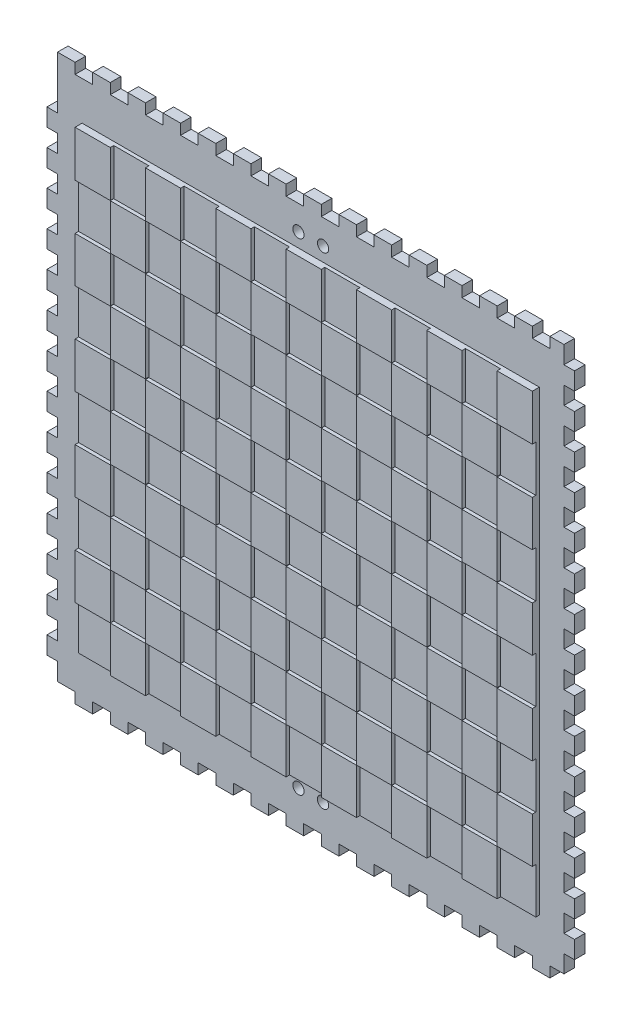
SolidWorks part; units mm, degrees
ref_plane "Front Plane" through (0, 0, 0) normal (0, 0, 1) x (1, 0, 0)
ref_plane "Top Plane" through (0, 0, 0) normal (0, 1, 0) x (1, 0, 0)
ref_plane "Right Plane" through (0, 0, 0) normal (1, 0, 0) x (0, 0, -1)
sketch "Sketch1" plane through (0, 0, 0) normal (0, 0, 1) x (1, 0, 0)
  line L1 (-75, 79) -> (75, 79)
  line L2 (-75, 79) -> (-75, -79)
  line L3 (-75, -79) -> (75, -79)
  line L4 (75, 79) -> (75, -79)
  line L5 (-75, 79) -> (75, -79) construction
  line L6 (-75, -79) -> (75, 79) construction
  point P0 (0, 0)
  dimension "D1" = 158
  dimension "D2" = 150
extrude "Boss-Extrude1" add sketch "Sketch1" along normal blind 5
sketch "Sketch2" plane through (0, 0, 5) normal (0, 0, 1) x (1, 0, 0)
  line L1 (-65, 65) -> (65, 65)
  line L2 (-65, 65) -> (-65, -65)
  line L3 (-65, -65) -> (65, -65)
  line L4 (65, 65) -> (65, -65)
  line L5 (-65, 65) -> (65, -65) construction
  line L6 (-65, -65) -> (65, 65) construction
  line L7 (-75, 79) -> (75, 79)
  line L8 (-75, 79) -> (-75, -79)
  line L9 (-75, -79) -> (75, -79)
  line L10 (75, 79) -> (75, -79)
  line L11 (-75, 79) -> (75, -79) construction
  line L12 (-75, -79) -> (75, 79) construction
  point P0 (0, 0)
  point P6 (0, 0)
  dimension "D1" = 130
  dimension "D2" = 130
extrude "Cut-Extrude1" cut sketch "Sketch2" against normal blind 2
sketch "Sketch3" plane through (0, 0, 5) normal (0, 0, 1) x (1, 0, 0)
  line L0 (-65, 65) -> (-65, -65) construction
  line L1 (-65, 51.95) -> (-55, 51.95)
  line L2 (-65, 51.95) -> (-65, 38.85)
  line L3 (-65, 38.85) -> (-55, 38.85)
  line L4 (-55, 51.95) -> (-55, 38.85)
  line L5 (65, 65) -> (-65, 65) construction
  dimension "D1" = 13.1
  dimension "D2" = 10
  dimension "D3" = 13.05
extrude "Cut-Extrude2" cut sketch "Sketch3" against normal blind 1
pattern_linear "LPattern1" count 7 spacing 20 along (1, 0, 0) count 5 spacing 26 along (0, -1, 0) of "Cut-Extrude2"
sketch "Sketch4" plane through (0, 0, 5) normal (0, 0, 1) x (1, 0, 0)
  line L0 (65, 65) -> (-65, 65) construction
  line L1 (-55, 65) -> (-45, 65)
  line L2 (-55, 65) -> (-55, 51.9)
  line L3 (-55, 51.9) -> (-45, 51.9)
  line L4 (-45, 65) -> (-45, 51.9)
  line L6 (-65, 65) -> (-65, -65) construction
  dimension "D1" = 10
  dimension "D2" = 10
  dimension "D3" = 13.1
extrude "Cut-Extrude3" cut sketch "Sketch4" against normal blind 1
pattern_linear "LPattern2" count 6 spacing 20 along (1, 0, 0) count 5 spacing 26 along (0, -1, 0) of "Cut-Extrude3"
sketch "Sketch5" plane through (0, 0, 3) normal (0, 0, 1) x (1, 0, 0)
  line L0 (-75, 79) -> (-75, -79) construction
  line L1 (-75, 64) -> (-72, 64)
  line L2 (-75, 64) -> (-75, 79)
  line L3 (-75, 79) -> (-72, 79)
  line L4 (-72, 64) -> (-72, 79)
  line L5 (75, 79) -> (-75, 79) construction
  dimension "D1" = 15
  dimension "D2" = 3
extrude "Cut-Extrude4" cut sketch "Sketch5" against normal blind 10
sketch "Sketch6" plane through (0, 0, 3) normal (0, 0, 1) x (1, 0, 0)
  line L0 (-75, 64) -> (-75, -79) construction
  line L1 (-75, 59) -> (-72, 59)
  line L2 (-75, 59) -> (-75, 54)
  line L3 (-75, 54) -> (-72, 54)
  line L4 (-72, 59) -> (-72, 54)
  line L5 (-75, 64) -> (-72, 64) construction
  dimension "D1" = 5
  dimension "D2" = 5
  dimension "D3" = 3
extrude "Cut-Extrude5" cut sketch "Sketch6" against normal blind 10
pattern_linear "LPattern3" count 14 spacing 10 along (0, -1, 0) of "Cut-Extrude5"
sketch "Sketch7" plane through (0, 0, 3) normal (0, 0, 1) x (1, 0, 0)
  line L1 (-72, -76) -> (-75, -76)
  line L2 (-72, -76) -> (-72, -79)
  line L3 (-72, -79) -> (-75, -79)
  line L4 (-75, -76) -> (-75, -79)
extrude "Cut-Extrude6" cut sketch "Sketch7" against normal blind 10
sketch "Sketch8" plane through (0, 0, 3) normal (0, 0, 1) x (1, 0, 0)
  line L1 (75, -79) -> (72, -79)
  line L2 (75, -79) -> (75, -71)
  line L3 (75, -71) -> (72, -71)
  line L4 (72, -79) -> (72, -71)
  dimension "D1" = 3
  dimension "D2" = 8
extrude "Cut-Extrude7" cut sketch "Sketch8" against normal blind 10
sketch "Sketch9" plane through (0, 0, 3) normal (0, 0, 1) x (1, 0, 0)
  line L0 (75, -71) -> (75, 79) construction
  line L1 (75, -66) -> (72, -66)
  line L2 (75, -66) -> (75, -61)
  line L3 (75, -61) -> (72, -61)
  line L4 (72, -66) -> (72, -61)
  line L5 (75, -71) -> (72, -71) construction
  dimension "D1" = 5
  dimension "D2" = 5
  dimension "D3" = 3
extrude "Cut-Extrude8" cut sketch "Sketch9" against normal blind 10
pattern_linear "LPattern4" count 15 spacing 10 along (0, 1, 0) of "Cut-Extrude8"
sketch "Sketch10" plane through (0, 0, 3) normal (0, 0, 1) x (1, 0, 0)
  line L0 (72, 79) -> (-72, 79) construction
  line L1 (-67, 79) -> (-62, 79)
  line L2 (-67, 79) -> (-67, 76)
  line L3 (-67, 76) -> (-62, 76)
  line L4 (-62, 79) -> (-62, 76)
  line L5 (-72, 64) -> (-72, 79) construction
  dimension "D1" = 3
  dimension "D2" = 5
  dimension "D3" = 5
extrude "Cut-Extrude9" cut sketch "Sketch10" against normal blind 10
pattern_linear "LPattern5" count 14 spacing 10 along (1, 0, 0) of "Cut-Extrude9"
sketch "Sketch11" plane through (0, 0, 3) normal (0, 0, 1) x (1, 0, 0)
  line L1 (-72, -79) -> (-67, -79)
  line L2 (-72, -79) -> (-72, -76)
  line L3 (-72, -76) -> (-67, -76)
  line L4 (-67, -79) -> (-67, -76)
  dimension "D1" = 3
  dimension "D2" = 5
extrude "Cut-Extrude10" cut sketch "Sketch11" against normal blind 3
pattern_linear "LPattern6" count 15 spacing 10 along (1, 0, 0) of "Cut-Extrude10"
sketch "Sketch12" plane through (0, 0, 3) normal (0, 0, 1) x (1, 0, 0)
  line L0 (-7, 76) -> (-2, 76) construction
  line L1 (3, 76) -> (8, 76) construction
  circle A0 centre (3.5, 69) radius 1.6
  circle A1 centre (-3.5, 69) radius 1.6
  dimension "D1" = 3.2
  dimension "D2" = 3.2
  dimension "D3" = 3.5
  dimension "D4" = 3.5
  dimension "D5" = 7
  dimension "D6" = 7
extrude "Cut-Extrude11" cut sketch "Sketch12" against normal blind 15
sketch "Sketch13" plane through (0, 0, 3) normal (0, 0, 1) x (1, 0, 0)
  line L0 (3, -76) -> (-2, -76) construction
  circle A0 centre (3.5, -68) radius 1.6
  circle A1 centre (-3.5, -68) radius 1.6
  dimension "D1" = 3.2
  dimension "D2" = 3.2
  dimension "D3" = 3.5
  dimension "D4" = 3.5
  dimension "D5" = 8
  dimension "D6" = 8
extrude "Cut-Extrude12" cut sketch "Sketch13" against normal blind 10
